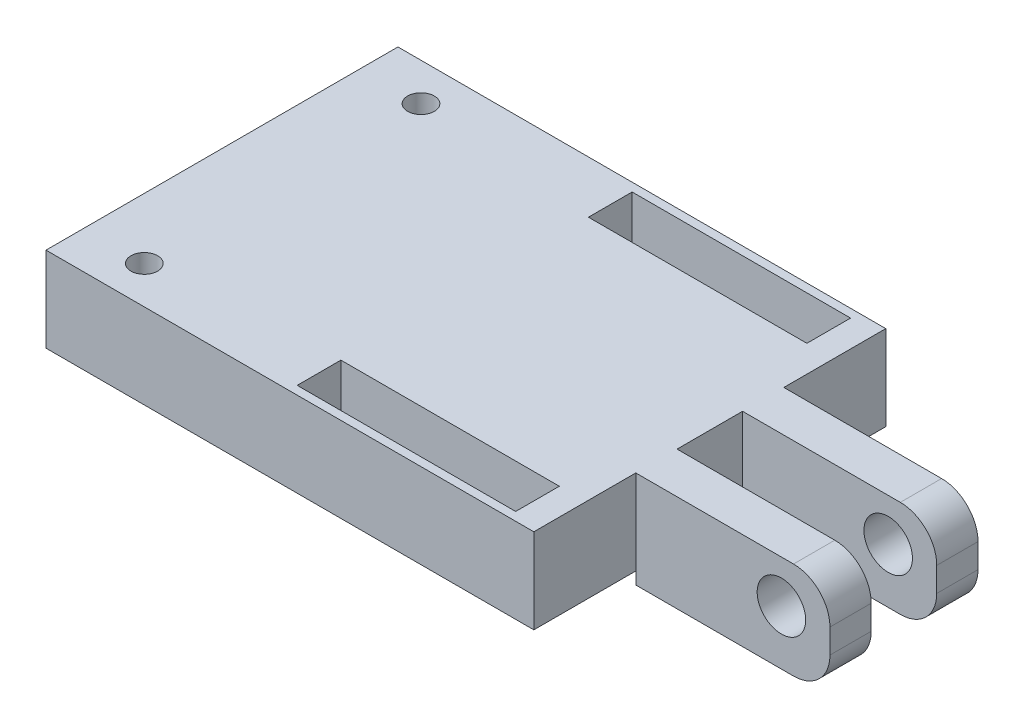
SolidWorks part; units mm, degrees
material "Custom Plastic"
ref_plane "Front Plane" through (0, 0, 0) normal (0, 0, 1) x (1, 0, 0)
ref_plane "Top Plane" through (0, 0, 0) normal (0, 1, 0) x (1, 0, 0)
ref_plane "Right Plane" through (0, 0, 0) normal (1, 0, 0) x (0, 0, -1)
sketch "Sketch2" plane through (0, 0, 0) normal (0, 1, 0) x (1, 0, 0)
  line L1 (-25.4, 18.415) -> (25.4, 18.415)
  line L2 (-25.4, 18.415) -> (-25.4, -18.415)
  line L3 (-25.4, -18.415) -> (25.4, -18.415)
  line L4 (25.4, 18.415) -> (25.4, -18.415)
  line L5 (-25.4, 18.415) -> (25.4, -18.415) construction
  line L6 (-25.4, -18.415) -> (25.4, 18.415) construction
  point P0 (0, 0)
  point P6 (0, 18.415)
  point P7 (0, -18.415)
  dimension "D1" = 50.8
  dimension "D2" = 36.83
extrude "Boss-Extrude1" add sketch "Sketch2" against normal blind 8.89 separate body
sketch "Sketch14" plane through (25.4, 0, 0) normal (1, 0, 0) x (0, 0, -1)
  line L13 (-18.415, 0) -> (18.415, 0)
  line L14 (-18.415, 0) -> (-18.415, -8.89)
  line L15 (-18.415, -8.89) -> (18.415, -8.89)
  line L17 (18.415, 0) -> (18.415, -8.89)
extrude "Boss-Extrude6" add sketch "Sketch14" along normal blind 0.254
sketch "Sketch15" plane through (25.654, 0, 0) normal (1, 0, 0) x (0, 0, -1)
  line L1 (-7.747, 0) -> (-3.429, 0)
  line L2 (-7.747, 0) -> (-7.747, -10.16)
  line L3 (-7.747, -10.16) -> (-3.429, -10.16)
  line L4 (-3.429, 0) -> (-3.429, -10.16)
  line L5 (-7.747, 0) -> (-3.429, -10.16) construction
  line L6 (-7.747, -10.16) -> (-3.429, 0) construction
  line L7 (3.429, 0) -> (7.747, 0)
  line L8 (3.429, 0) -> (3.429, -10.16)
  line L9 (3.429, -10.16) -> (7.747, -10.16)
  line L10 (7.747, 0) -> (7.747, -10.16)
  line L11 (3.429, 0) -> (7.747, -10.16) construction
  line L12 (3.429, -10.16) -> (7.747, 0) construction
  line L13 (-18.415, 0) -> (-18.415, -8.89) construction
  line L14 (-18.415, 0) -> (-18.415, -8.89)
  line L15 (-5.588, -5.08) -> (5.588, -5.08) construction
  point P0 (-5.588, -5.08)
  point P5 (5.588, -5.08)
  point P10 (0, -5.08)
  point P21 (-5.588, 0)
  dimension "D1" = 4.318
  dimension "D2" = 6.858
  dimension "D3" = 10.16
extrude "Boss-Extrude7" add sketch "Sketch15" along normal blind 20.32 contours L4 L3 L2 L1 | L10 L9 L8 L7
sketch "Sketch16" plane through (0, 0, -7.747) normal (0, 0, -1) x (-1, 0, 0)
  line L0 (-25.654, -8.89) -> (-25.654, 0) construction
  line L1 (-45.974, 0) -> (-25.654, 0) construction
  line L2 (-25.654, -8.89) -> (-25.654, 0)
  line L3 (-45.974, 0) -> (-25.654, 0)
  line L4 (-45.974, 0) -> (-45.974, -10.16) construction
  circle A0 centre (-40.894, -4.445) radius 2.54
  point P9 (-25.654, -4.445)
  dimension "D1" = 5.08
  dimension "D2" = 5.08
extrude "Cut-Extrude3" cut sketch "Sketch16" against normal through all both and the other way through all contours A0
fillet "Fillet1" radius 3.81 4 edges at (45.974, 0, 5.588) (45.974, -10.16, 5.588) (45.974, 0, -5.588) (45.974, -10.16, -5.588)
sketch "Sketch18" plane through (0, 0, 0) normal (0, 1, 0) x (1, 0, 0)
  line L1 (-22.352, 17.78) -> (22.352, 17.78)
  line L2 (-22.352, 17.78) -> (-22.352, -17.78)
  line L3 (-22.352, -17.78) -> (22.352, -17.78)
  line L4 (22.352, 17.78) -> (22.352, -17.78)
  line L5 (-22.352, 17.78) -> (22.352, -17.78) construction
  line L6 (-22.352, -17.78) -> (22.352, 17.78) construction
  line L7 (0, -12.954) -> (22.86, -12.954)
  line L8 (0, -12.954) -> (0, -17.526)
  line L9 (0, -17.526) -> (22.86, -17.526)
  line L10 (22.86, -12.954) -> (22.86, -17.526)
  line L11 (0, -12.954) -> (22.86, -17.526) construction
  line L12 (0, -17.526) -> (22.86, -12.954) construction
  line L13 (0, 17.526) -> (22.86, 17.526)
  line L14 (0, 17.526) -> (0, 12.954)
  line L15 (0, 12.954) -> (22.86, 12.954)
  line L16 (22.86, 17.526) -> (22.86, 12.954)
  line L17 (0, 17.526) -> (22.86, 12.954) construction
  line L18 (0, 12.954) -> (22.86, 17.526) construction
  circle A0 centre (-19.05, -14.478) radius 1.397
  circle A1 centre (-19.05, 14.478) radius 1.397
  point P0 (0, 0)
  point P10 (11.43, -15.24)
  point P15 (11.43, 15.24)
  dimension "D3" = 2.794
  dimension "D4" = 2.794
  dimension "D1" = 44.704
  dimension "D2" = 35.56
  dimension "D5" = 28.956
  dimension "D6" = 3.302
  dimension "D7" = 3.302
  dimension "D8" = 3.302
  dimension "D9" = 30.48
  dimension "D10" = 30.48
  dimension "D11" = 4.572
  dimension "D12" = 4.572
  dimension "D13" = 22.86
  dimension "D14" = 22.86
  dimension "D15" = 0.254
  dimension "D16" = 0.254
extrude "Cut-Extrude5" cut sketch "Sketch18" against normal blind 2.286 contours A1 | A0
extrude "Cut-Extrude6" cut sketch "Sketch18<5>" against normal blind 7.62 contours L15 L16 L13 L14
sketch "Sketch18<5>" plane through (0, 0, 0) normal (0, 1, 0) x (1, 0, 0) same geometry as "Sketch18"
extrude "Cut-Extrude7" cut sketch "Sketch18<6>" against normal blind 7.62 contours L9 L10 L7 L8
sketch "Sketch18<6>" plane through (0, 0, 0) normal (0, 1, 0) x (1, 0, 0) same geometry as "Sketch18"
